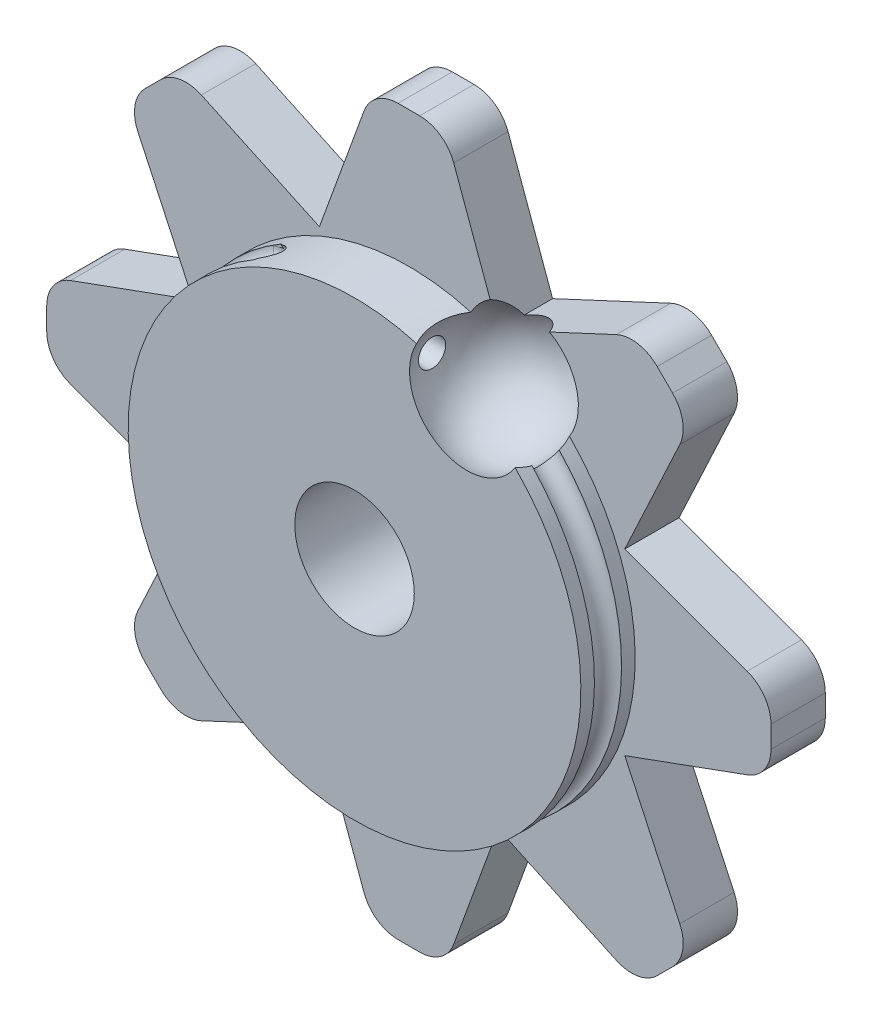
SolidWorks part; units mm, degrees
ref_plane "Front Plane" through (0, 0, 0) normal (0, 0, 1) x (1, 0, 0)
ref_plane "Top Plane" through (0, 0, 0) normal (0, 1, 0) x (1, 0, 0)
ref_plane "Right Plane" through (0, 0, 0) normal (1, 0, 0) x (0, 0, -1)
ref_axis "Axis1" through (-11, 0, 0) along (1, 0, 0)
ref_axis "Axis2" through (0, 0, 2.0438) along (0, 0, -1)
ref_plane "Plane5" through (0, 0, 0) normal (0.866, 0.5, 0) x (0, 0, -1)
ref_plane "Plane6" through (3.1, 0, 0) normal (1, 0, 0) x (0, 0, -1)
sketch "Sketch1" plane through (0, 0, 0) normal (0, 0, 1) x (1, 0, 0)
  line L0 (-11, 0) -> (11, 0) construction
  circle A0 centre (0, 0) radius 6.25
  dimension "D1" = 12.5
extrude "body" add sketch "Sketch1" along normal blind 1.5 contours A0
sketch "Sketch2" plane through (0, 0, 0) normal (1, 0, 0) x (0, 0, -1)
  line L1 (0, 6.25) -> (-1.5, 6.25) construction
  line L2 (0, 5.25) -> (-1.5, 5.25) construction
  line L3 (-0.75, 5.25) -> (-0.75, -4.75) construction
  line L4 (0, -6.25) -> (0, 6.25) construction
  line L5 (0, -6.25) -> (0, 6.25) construction
  circle A0 centre (-0.75, 5.25) radius 0.375
  circle A1 centre (-0.75, -4.75) radius 0.375
  dimension "D1" = 0.75
  dimension "D3" = 0.75
  dimension "D4" = 1.5
  dimension "D2" = 1
extrude "Hole to trap cable knot" cut sketch "Sketch2" against normal through all and the other way blind 10 contours A0 | A1
ref_plane "Plane1" through (0, 0, 1.875) normal (0, 0, 1) x (1, 0, 0)
sketch "Sketch6" plane through (0, 0, 1.875) normal (0, 0, 1) x (1, 0, 0)
  line L0 (1.0209, -1.7683) -> (-1.0209, 1.7683) construction
  arc A0 (3.9111, 4.875) -> (2.7243, 5.625) centre (0, 0) ccw construction
  circle A2 centre (0, 0) radius 6.25 construction
  arc A3 (-3.125, 5.4127) -> (3.2608, 5.332) centre (0, 0) ccw
  arc A4 (3.9111, 4.875) -> (2.7243, 5.625) centre (0, 0) ccw construction
sketch "Sketch10" plane through (-5.4127, 9.375, 0) normal (-0.866, -0.5, 0) x (-0.5, 0.866, 0)
  line L0 (-4.5831, -1.125) -> (-3.8727, -1.125)
  line L1 (-3.8727, -1.125) -> (-3.8727, -0.3748)
  line L2 (-3.8727, -0.3748) -> (-4.5831, -0.3748)
  arc A0 (-4.5831, -0.3748) -> (-4.5831, -1.125) centre (-4.5831, -0.7499) ccw
  spline S0 degree 3 poles (-4.5903, -1.125) (-4.5759, -1.125) (-4.5739, -1.1025) (-4.5775, -1.0318) (-4.5799, -1.0018) (-4.5843, -0.9422) (-4.5859, -0.9199) (-4.589, -0.8665) (-4.5904, -0.8353) (-4.592, -0.7664) (-4.5919, -0.7281) (-4.5902, -0.6593) (-4.5887, -0.6289) (-4.5841, -0.5506) (-4.5809, -0.5129) (-4.5744, -0.422) (-4.574, -0.3902) (-4.5837, -0.3678) (-4.5938, -0.3778) (-4.6147, -0.4453) (-4.6227, -0.4771) (-4.6376, -0.5669) (-4.6447, -0.6281) (-4.6494, -0.7694) (-4.6461, -0.8461) (-4.6338, -0.9631) (-4.6257, -1.0065) (-4.603, -1.1026) (-4.5903, -1.125) (-4.5759, -1.125) (-4.5739, -1.1025) knots -0.125 -0.125 0 0 0.125 0.125 0.1875 0.1875 0.21875 0.21875 0.25 0.25 0.28125 0.28125 0.3125 0.3125 0.375 0.375 0.5 0.5 0.625 0.625 0.6875 0.6875 0.75 0.75 0.8125 0.8125 0.875 0.875 1 1 1.125 1.125 1.1875 only from (-4.5831, -1.125) to (-4.5831, -1.125) construction
  spline S1 degree 3 poles (-4.5903, -1.125) (-4.5759, -1.125) (-4.5739, -1.1025) (-4.5775, -1.0318) (-4.5799, -1.0018) (-4.5843, -0.9422) (-4.5859, -0.9199) (-4.589, -0.8665) (-4.5904, -0.8353) (-4.592, -0.7664) (-4.5919, -0.7281) (-4.5902, -0.6593) (-4.5887, -0.6289) (-4.5841, -0.5506) (-4.5809, -0.5129) (-4.5744, -0.422) (-4.574, -0.3902) (-4.5837, -0.3678) (-4.5938, -0.3778) (-4.6147, -0.4453) (-4.6227, -0.4771) (-4.6376, -0.5669) (-4.6447, -0.6281) (-4.6494, -0.7694) (-4.6461, -0.8461) (-4.6338, -0.9631) (-4.6257, -1.0065) (-4.603, -1.1026) (-4.5903, -1.125) (-4.5759, -1.125) (-4.5739, -1.1025) knots -0.125 -0.125 0 0 0.125 0.125 0.1875 0.1875 0.21875 0.21875 0.25 0.25 0.28125 0.28125 0.3125 0.3125 0.375 0.375 0.5 0.5 0.625 0.625 0.6875 0.6875 0.75 0.75 0.8125 0.8125 0.875 0.875 1 1 1.125 1.125 1.1875 only from (-4.5831, -1.125) to (-4.5831, -1.125) construction
  point P1 (-4.5831, -0.3748)
sweep "track for cable" cut profiles "Sketch10" path "Sketch6"
sketch "Sketch12" plane through (0, 0, 0) normal (0, 0, -1) x (-1, 0, 0)
  line L0 (0, 10) -> (0, -10) construction
  line L1 (-2.5653, 5.6993) -> (-1.2395, 9.342)
  line L2 (-0.2998, 10) -> (0.2998, 10)
  line L3 (1.2395, 9.342) -> (2.5653, 5.6993)
  line L6 (-3.2365, 3.8554) -> (3.2365, 3.8554) construction
  line L7 (-2.5653, 5.6993) -> (0, 0)
  line L8 (0, 0) -> (2.5653, 5.6993)
  arc A0 (-1.2395, 9.342) -> (-0.2998, 10) centre (-0.2998, 9) cw
  arc A1 (0.2998, 10) -> (1.2395, 9.342) centre (0.2998, 9) cw
  circle A4 centre (0, 0) radius 6.25 construction
  point P9 (-1, 10)
  point P12 (1, 10)
  dimension "D6" = 1
  dimension "D1" = 20
  dimension "D2" = 2
  dimension "D3" = 6.4729
  dimension "D4" = 110
  dimension "D5" = 110
sketch "Sketch14" plane through (0, 0, 0) normal (0, 0, -1) x (-1, 0, 0)
  line L0 (5.7294, 7.4823) -> (2.4696, 5.9622)
  line L1 (7.2831, 6.8591) -> (6.8591, 7.2831)
  line L2 (5.9622, 2.4696) -> (7.4823, 5.7294)
  line L3 (0, 0) -> (5.844, 2.216) construction
  line L4 (2.216, 5.844) -> (0, 0) construction
  line L5 (-1.2395, 9.342) -> (-2.5653, 5.6993)
  line L6 (0.2998, 10) -> (-0.2998, 10)
  line L7 (2.5653, 5.6993) -> (1.2395, 9.342)
  line L8 (0, 0) -> (2.5653, 5.6993)
  line L9 (0, 0) -> (2.5653, 5.6993) construction
  line L10 (-1.2395, 9.342) -> (-2.4696, 5.9622)
  line L11 (0.2998, 10) -> (-0.2998, 10)
  line L12 (2.4696, 5.9622) -> (1.2395, 9.342)
  line L13 (-2.5653, 5.6993) -> (0, 0)
  line L14 (-2.5653, 5.6993) -> (0, 0) construction
  line L15 (9.342, 1.2395) -> (5.9622, 2.4696)
  line L16 (10, -0.2998) -> (10, 0.2998)
  line L17 (5.9622, -2.4696) -> (9.342, -1.2395)
  line L18 (0, 0) -> (5.6993, -2.5653) construction
  line L19 (5.6993, 2.5653) -> (0, 0) construction
  line L20 (7.4823, -5.7294) -> (5.9622, -2.4696)
  line L21 (6.8591, -7.2831) -> (7.2831, -6.8591)
  line L22 (2.4696, -5.9622) -> (5.7294, -7.4823)
  line L23 (0, 0) -> (2.216, -5.844) construction
  line L24 (5.844, -2.216) -> (0, 0) construction
  line L25 (1.2395, -9.342) -> (2.4696, -5.9622)
  line L26 (-0.2998, -10) -> (0.2998, -10)
  line L27 (-2.4696, -5.9622) -> (-1.2395, -9.342)
  line L28 (0, 0) -> (-2.5653, -5.6993) construction
  line L29 (2.5653, -5.6993) -> (0, 0) construction
  line L30 (-5.7294, -7.4823) -> (-2.4696, -5.9622)
  line L31 (-7.2831, -6.8591) -> (-6.8591, -7.2831)
  line L32 (-5.9622, -2.4696) -> (-7.4823, -5.7294)
  line L33 (0, 0) -> (-5.844, -2.216) construction
  line L34 (-2.216, -5.844) -> (0, 0) construction
  line L35 (-9.342, -1.2395) -> (-5.9622, -2.4696)
  line L36 (-10, 0.2998) -> (-10, -0.2998)
  line L37 (-5.9622, 2.4696) -> (-9.342, 1.2395)
  line L38 (0, 0) -> (-5.6993, 2.5653) construction
  line L39 (-5.6993, -2.5653) -> (0, 0) construction
  line L40 (-7.4823, 5.7294) -> (-5.9622, 2.4696)
  line L41 (-6.8591, 7.2831) -> (-7.2831, 6.8591)
  line L42 (-2.4696, 5.9622) -> (-5.7294, 7.4823)
  line L43 (0, 0) -> (-2.216, 5.844) construction
  line L44 (-5.844, 2.216) -> (0, 0) construction
  arc A0 (6.8591, 7.2831) -> (5.7294, 7.4823) centre (6.152, 6.5759) ccw
  arc A1 (7.4823, 5.7294) -> (7.2831, 6.8591) centre (6.5759, 6.152) ccw
  arc A2 (-0.2998, 10) -> (-1.2395, 9.342) centre (-0.2998, 9) ccw
  arc A3 (1.2395, 9.342) -> (0.2998, 10) centre (0.2998, 9) ccw
  arc A4 (-0.2998, 10) -> (-1.2395, 9.342) centre (-0.2998, 9) ccw
  arc A5 (1.2395, 9.342) -> (0.2998, 10) centre (0.2998, 9) ccw
  arc A6 (10, 0.2998) -> (9.342, 1.2395) centre (9, 0.2998) ccw
  arc A7 (9.342, -1.2395) -> (10, -0.2998) centre (9, -0.2998) ccw
  arc A8 (7.2831, -6.8591) -> (7.4823, -5.7294) centre (6.5759, -6.152) ccw
  arc A9 (5.7294, -7.4823) -> (6.8591, -7.2831) centre (6.152, -6.5759) ccw
  arc A10 (0.2998, -10) -> (1.2395, -9.342) centre (0.2998, -9) ccw
  arc A11 (-1.2395, -9.342) -> (-0.2998, -10) centre (-0.2998, -9) ccw
  arc A12 (-6.8591, -7.2831) -> (-5.7294, -7.4823) centre (-6.152, -6.5759) ccw
  arc A13 (-7.4823, -5.7294) -> (-7.2831, -6.8591) centre (-6.5759, -6.152) ccw
  arc A14 (-10, -0.2998) -> (-9.342, -1.2395) centre (-9, -0.2998) ccw
  arc A15 (-9.342, 1.2395) -> (-10, 0.2998) centre (-9, 0.2998) ccw
  arc A16 (-7.2831, 6.8591) -> (-7.4823, 5.7294) centre (-6.5759, 6.152) ccw
  arc A17 (-5.7294, 7.4823) -> (-6.8591, 7.2831) centre (-6.152, 6.5759) ccw
  point P67 (0, 0)
  dimension "D1" = 0
  dimension "D2" = 8
extrude "thumb grip" add sketch "Sketch14" along normal blind 1.5
sketch "Sketch13" plane through (0, 0, 1.5) normal (0, 0, 1) x (1, 0, 0)
  circle A0 centre (0, 0) radius 1.65
  dimension "D1" = 3.3
extrude "hole for screw" cut sketch "Sketch13" against normal through all
sketch "Sketch20" plane through (3.1, 0, 0) normal (1, 0, 0) x (0, 0, -1)
  line L0 (-0.75, 7) -> (-0.75, 3.5)
  line L1 (-0.75, 7.7934) -> (-0.75, 1.6513) construction
  circle A0 centre (-0.75, 5.25) radius 1.75 construction
  arc A1 (-0.3841, 5.332) -> (-1.1159, 5.332) centre (-0.75, 5.25) ccw construction
  arc A2 (-0.3841, 5.332) -> (-1.1159, 5.332) centre (-0.75, 5.25) ccw construction
  arc A3 (-0.75, 7) -> (-0.75, 3.5) centre (-0.75, 5.25) cw
  dimension "D1" = 3.5
revolve "trap for ball" cut sketch "Sketch20" angle 360 about L1
sketch "Sketch21" plane through (0, 0, 1.5) normal (0, 0, 1) x (1, 0, 0)
  circle A0 centre (0, 0) radius 2.8716
  circle A3 centre (0, 0) radius 1.65 construction
  circle A4 centre (0, 0) radius 1.65
extrude "lip to contact handle" [suppressed] add sketch "Sketch21" along normal blind 0.25 and the other way blind 3.75
fillet "Fillet1" [suppressed] radius 0.1
equation "\"Do\"=8.5mm"
equation "\"Lo\"=10"
equation "\"screw_diam\" = 3.5mm"
equation "\"wheel_Do\"=12.5mm"
equation "\"wheel_thickness\"=4mm"
equation "\"Collet_diameter\"=4.3"
equation "\"clearance\"= 0.5mm"
equation "\"D1@Sketch1\"=\"wheel_Do\""
equation "\"wheel_total_diam_ent\"=20"
equation "\"D1@Sketch12\"=\"wheel_total_diam_ent\""
equation "\"handle_body_width\" = 10mm"
equation "\"finger_diameter\"=35"
equation "\"collet_lid_diameter\"=10"
equation "\"screw_cap_diam\"=5.15"
equation "\"handle_thickness\"=12.5mm"
equation "\"post_hole_diam\"=2"
equation "\"roll_rod_diam\"= 6.5 "
equation "\"roll_rod_length\"=6.6"
equation "\"disc_diam\"=5"
equation "\"disc_width\"=1.5"
equation "\"arm_width\"=5"
equation "\"arm_thickness\"=4.5"
equation "\"wheel_total_diam\"=30"
equation "\"D1@thumb grip\"=\"wheel_thickness\"-2.5"
equation "\"D1@body\"=\"wheel_thickness\""
